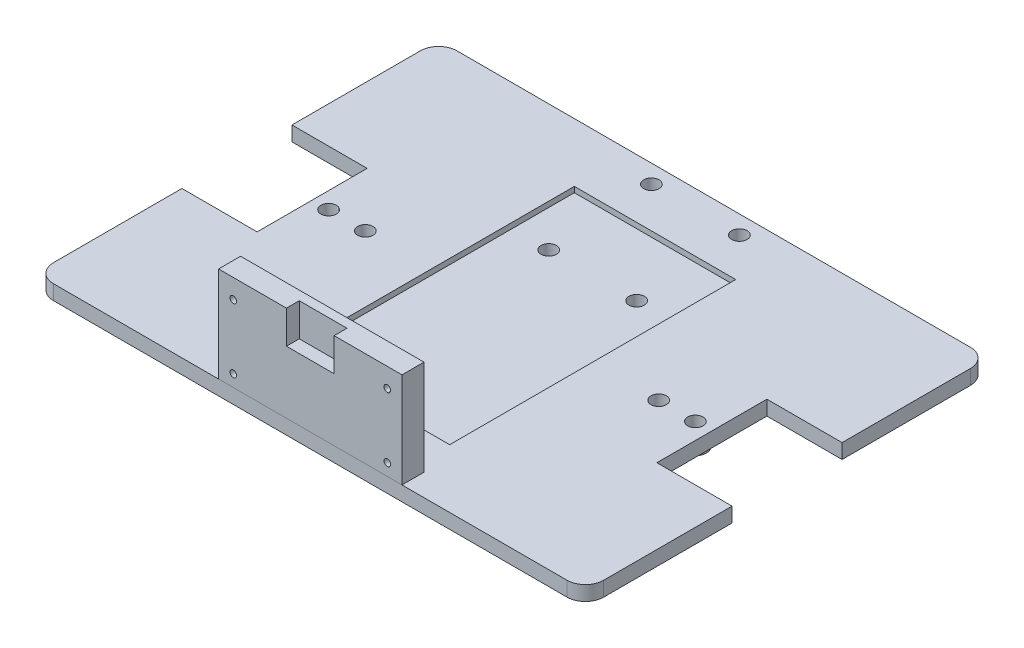
SolidWorks part; units mm, degrees
ref_plane "Front Plane" through (0, 0, 0) normal (0, 0, 1) x (1, 0, 0)
ref_plane "Top Plane" through (0, 0, 0) normal (0, 1, 0) x (1, 0, 0)
ref_plane "Right Plane" through (0, 0, 0) normal (1, 0, 0) x (0, 0, -1)
sketch "Sketch1" plane through (0, 0, 0) normal (0, 1, 0) x (1, 0, 0)
  line L0 (-75, 0) -> (75, 0) construction
  line L1 (-75, -55) -> (75, -55)
  line L2 (-75, -55) -> (-75, 55)
  line L3 (-75, 55) -> (75, 55)
  line L4 (75, -55) -> (75, 55)
  line L5 (-75, -55) -> (75, 55) construction
  line L6 (-75, 55) -> (75, -55) construction
  point P0 (0, 0)
  dimension "D1" = 150
  dimension "D2" = 110
extrude "Boss-Extrude1" add sketch "Sketch1" along normal blind 4
fillet "Fillet1" radius 5 4 edges at (-75, 2, -55) (-75, 2, 55) (75, 2, -55) (75, 2, 55)
sketch "Sketch2" plane through (0, 4, 0) normal (0, 1, 0) x (1, 0, 0)
  line L0 (-75, 0) -> (75, 0) construction
  line L1 (-75, 50) -> (-75, -50) construction
  line L2 (75, -50) -> (75, 50) construction
  line L3 (0, 55) -> (0, -55) construction
  line L4 (70, 55) -> (-70, 55) construction
  line L5 (-70, -55) -> (70, -55) construction
  circle A0 centre (-50, 0) radius 2.1
  circle A1 centre (-40, 0) radius 2.1
  dimension "D1" = 4.2
  dimension "D2" = 50
  dimension "D3" = 4.2
  dimension "D4" = 40
extrude "Cut-Extrude1" cut sketch "Sketch2" against normal through all
sketch "Sketch3" plane through (0, 0, 0) normal (0, -1, 0) x (1, 0, 0)
  line L0 (-75, 0) -> (75, 0) construction
  line L1 (-75, -50) -> (-75, 50) construction
  line L2 (75, 50) -> (75, -50) construction
  line L3 (0, 55) -> (0, -55) construction
  line L4 (-70, 55) -> (70, 55) construction
  line L5 (70, -55) -> (-70, -55) construction
  circle A0 centre (-50, 0) radius 3
  circle A1 centre (-40, 0) radius 3
  dimension "D1" = 6
  dimension "D2" = 6
extrude "Boss-Extrude2" add sketch "Sketch3" along normal blind 2
mirror "Mirror1" about plane through (0, 0, 0) normal (1, 0, 0) of "Boss-Extrude2", "Cut-Extrude1"
sketch "Sketch4" plane through (0, 4, 0) normal (0, 1, 0) x (1, 0, 0)
  line L0 (0, -55) -> (0, 55) construction
  line L1 (-22, -39) -> (-6, -39)
  line L2 (-22, -39) -> (-22, 39)
  line L3 (-22, 39) -> (22, 39)
  line L4 (22, -39) -> (22, 39)
  line L5 (-22, -39) -> (22, 39) construction
  line L6 (-22, 39) -> (22, -39) construction
  line L7 (-70, -55) -> (70, -55) construction
  line L8 (70, 55) -> (-70, 55) construction
  line L9 (6, -39) -> (22, -39)
  line L10 (-6, -43) -> (6, -43)
  line L11 (-6, -43) -> (-6, -39)
  line L13 (6, -43) -> (6, -39)
  line L14 (-6, -43) -> (6, -39) construction
  line L15 (-6, -39) -> (6, -43) construction
  point P0 (0, 0)
  point P15 (0, -41)
  dimension "D1" = 44
  dimension "D2" = 78
  dimension "D3" = 0
  dimension "D4" = 4
  dimension "D5" = 12
extrude "Cut-Extrude2" cut sketch "Sketch4" against normal blind 1.5
sketch "Sketch7" plane through (0, 0, 55) normal (0, 0, 1) x (1, 0, 0)
  line L0 (-70, 4) -> (70, 4) construction
  line L1 (-25, 4) -> (25, 4)
  line L2 (-25, 4) -> (-25, 30)
  line L3 (-25, 30) -> (25, 30)
  line L4 (25, 4) -> (25, 30)
  line L5 (-25, 4) -> (25, 30) construction
  line L6 (-25, 30) -> (25, 4) construction
  line L7 (70, 0) -> (70, 4) construction
  point P0 (0, 17)
  point P7 (0, 0)
  point P8 (0, 0)
  point P9 (0, 17)
  point P10 (0, 30)
  dimension "D1" = 50
  dimension "D2" = 26
  dimension "D3" = 45
extrude "Boss-Extrude4" add sketch "Sketch7" against normal blind 6 separate body
sketch "Sketch10" plane through (0, 4, 0) normal (0, 1, 0) x (1, 0, 0)
  circle A0 centre (-50, 0) radius 2.1
  circle A1 centre (-40, 0) radius 2.1
  circle A2 centre (40, 0) radius 2.1
  circle A3 centre (50, 0) radius 2.1
  dimension "D1" = 4.2
  dimension "D2" = 4.2
  dimension "D3" = 4.2
  dimension "D4" = 4.2
extrude "Cut-Extrude5" cut sketch "Sketch10" against normal through all
sketch "Sketch11" plane through (0, 4, 0) normal (0, 1, 0) x (1, 0, 0)
  line L0 (75, -50) -> (75, 50) construction
  line L1 (54.5, -15) -> (75, -15)
  line L2 (54.5, -15) -> (54.5, 15)
  line L3 (54.5, 15) -> (75, 15)
  line L4 (75, -15) -> (75, 15)
  line L5 (54.5, -15) -> (75, 15) construction
  line L6 (54.5, 15) -> (75, -15) construction
  line L7 (0, -18.425) -> (0, 18.425) construction
  line L8 (-54.5, 15) -> (-75, -15) construction
  line L9 (-54.5, -15) -> (-75, 15) construction
  line L10 (-75, -15) -> (-75, 15)
  line L11 (-54.5, 15) -> (-75, 15)
  line L12 (-54.5, -15) -> (-54.5, 15)
  line L13 (-54.5, -15) -> (-75, -15)
  point P0 (64.75, 0)
  point P14 (-64.75, 0)
  dimension "D1" = 54.5
  dimension "D2" = 15
  dimension "D3" = 15
extrude "Cut-Extrude6" cut sketch "Sketch11" against normal through all
sketch "Sketch12" plane through (0, 0, 0) normal (0, -1, 0) x (1, 0, 0)
  line L0 (70, -55) -> (-70, -55) construction
  line L1 (-12, -50) -> (12, -50) construction
  line L2 (-12, -50) -> (-12, -22) construction
  line L3 (-12, -22) -> (12, -22) construction
  line L4 (12, -50) -> (12, -22) construction
  line L5 (-12, -50) -> (12, -22) construction
  line L6 (-12, -22) -> (12, -50) construction
  circle A0 centre (-12, -22) radius 4
  circle A1 centre (12, -22) radius 4
  circle A2 centre (12, -50) radius 4
  circle A3 centre (-12, -50) radius 4
  point P0 (0, -36)
  dimension "D4" = 8
  dimension "D1" = 24
  dimension "D2" = 28
  dimension "D3" = 5
extrude "Boss-Extrude5" add sketch "Sketch12" along normal blind 3.5
sketch "Sketch13" plane through (0, 4, 0) normal (0, 1, 0) x (1, 0, 0)
  circle A0 centre (12, 22) radius 2.1
  circle A4 centre (-12, 50) radius 2.1
  circle A6 centre (12, 50) radius 2.1
  circle A7 centre (-12, 22) radius 2.1
  dimension "D1" = 4.2
  dimension "D2" = 4.2
  dimension "D3" = 4.2
  dimension "D4" = 4.2
extrude "Cut-Extrude7" cut sketch "Sketch13" against normal through all
sketch "Sketch14" plane through (0, 0, 55) normal (0, 0, 1) x (1, 0, 0)
  line L0 (0, 4) -> (0, 30) construction
  line L1 (-25, 4) -> (25, 4) construction
  line L2 (25, 30) -> (-25, 30) construction
  circle A0 centre (-21, 24.75) radius 0.9
  circle A1 centre (-21, 7.25) radius 0.9
  circle A2 centre (21, 7.25) radius 0.9
  circle A3 centre (21, 24.75) radius 0.9
  dimension "D1" = 1.8
  dimension "D2" = 1.8
  dimension "D3" = 3.25
  dimension "D4" = 20.75
  dimension "D5" = 21
  dimension "D6" = 21
extrude "Cut-Extrude8" cut sketch "Sketch14" against normal blind 4.5
sketch "Sketch15" plane through (0, 0, 55) normal (0, 0, 1) x (1, 0, 0)
  line L0 (-25, 4) -> (25, 4) construction
  line L1 (-6.5, 30) -> (6.5, 30)
  line L2 (-6.5, 30) -> (-6.5, 21)
  line L3 (-6.5, 21) -> (6.5, 21)
  line L4 (6.5, 30) -> (6.5, 21)
  line L5 (-6.5, 30) -> (6.5, 21) construction
  line L6 (-6.5, 21) -> (6.5, 30) construction
  line L8 (25, 30) -> (-25, 30) construction
  point P0 (0, 25.5)
  point P7 (0, 0)
  point P8 (0, 0)
  point P11 (0, 0)
  dimension "D1" = 13
  dimension "D2" = 17
extrude "Cut-Extrude9" cut sketch "Sketch15" against normal blind 3.5
